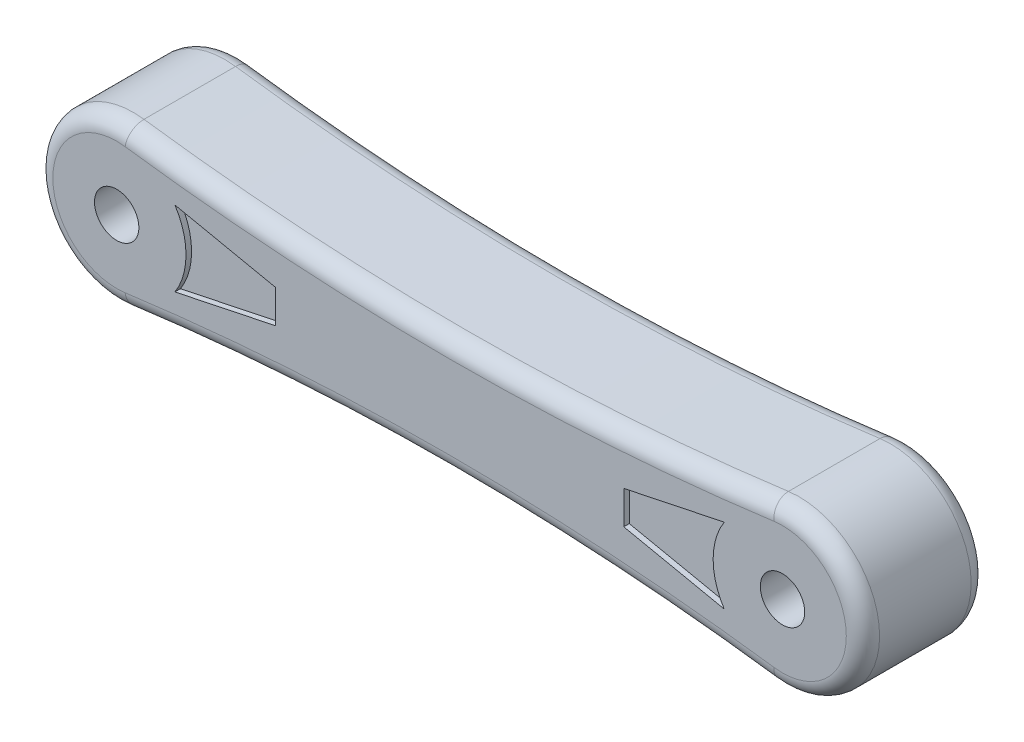
SolidWorks part; units mm, degrees
ref_plane "Plan de face" through (0, 0, 0) normal (0, 0, 1) x (1, 0, 0)
ref_plane "Plan de dessus" through (0, 0, 0) normal (0, 1, 0) x (1, 0, 0)
ref_plane "Plan de droite" through (0, 0, 0) normal (1, 0, 0) x (0, 0, -1)
other "Centre de masse"
sketch "Esquisse1" plane through (0, 0, 0) normal (0, 0, 1) x (1, 0, 0)
  line L0 (-26.8643, 0) -> (151.1286, 0) construction
  arc A0 (1.9248, 14.3717) -> (1.9248, -14.3717) centre (0, 0) ccw
  arc A1 (1.9248, 14.3717) -> (118.0752, 14.3717) centre (60, 448) ccw
  arc A2 (118.0752, -14.3717) -> (118.0752, 14.3717) centre (120, 0) ccw
  circle A3 centre (0, 0) radius 4
  circle A4 centre (120, 0) radius 4
  arc A5 (1.9248, -14.3717) -> (118.0752, -14.3717) centre (60, -448) cw
  point P2 (60, -10.5)
  point P5 (60, 10.5)
  point P14 (-14.5, 0)
  point P15 (134.5, 0)
  dimension "D1" = 4
  dimension "D2" = 14.5
  dimension "D3" = 10.5
  dimension "D4" = 149
extrude "Boss.-Extru.1" add sketch "Esquisse1" along normal blind 11.25 contours A0 L0 A3 A4 A2 A1 | L0 A0 A5 A2 A4 A3 region at (60, 6.1571, 0) region at (60, -6.1571, 0)
fillet "Congé1" radius 3 4 edges at (60, 10.5, 11.25) (134.5, 0, 11.25) (60, -10.5, 11.25) (-14.5, 0, 11.25)
mirror "Symétrie5" about plane through (0, 0, 0) normal (0, 0, 1) of "Congé1", "Boss.-Extru.1"
sketch "Esquisse3" plane through (0, 0, 11.25) normal (0, 0, 1) x (1, 0, 0)
  line L0 (10.5, 6.7823) -> (28.6092, 3)
  line L1 (28.6092, 3) -> (28.6092, -3)
  line L2 (28.6092, -3) -> (10.5, -6.7823)
  line L3 (60, 7.5) -> (60, -7.5) construction
  line L4 (91.3908, -3) -> (109.5, -6.7823)
  line L5 (91.3908, 3) -> (91.3908, -3)
  line L6 (109.5, 6.7823) -> (91.3908, 3)
  arc A0 (10.5, 6.7823) -> (10.5, -6.7823) centre (0, 0) cw
  circle A1 centre (0, 0) radius 4 construction
  arc A3 (1.5265, 11.3982) -> (118.4735, 11.3982) centre (60, 448) ccw construction
  arc A4 (118.4735, -11.3982) -> (1.5265, -11.3982) centre (60, -448) ccw construction
  arc A5 (109.5, 6.7823) -> (109.5, -6.7823) centre (120, 0) ccw
  point P21 (107.5, 0)
  point P23 (12.5, 0)
  dimension "D1" = 12.5
  dimension "D2" = 18.5
  dimension "D3" = 6
  dimension "D4" = 2
extrude "Enlèv. mat.-Extru.1" cut sketch "Esquisse3" against normal blind 1
mirror "Symétrie6" about plane through (0, 0, 0) normal (0, 0, 1) of "Enlèv. mat.-Extru.1"
ref_axis "Axe1" through (120, 0, 11.25) along (0, 0, -1)
ref_point "Point1"
